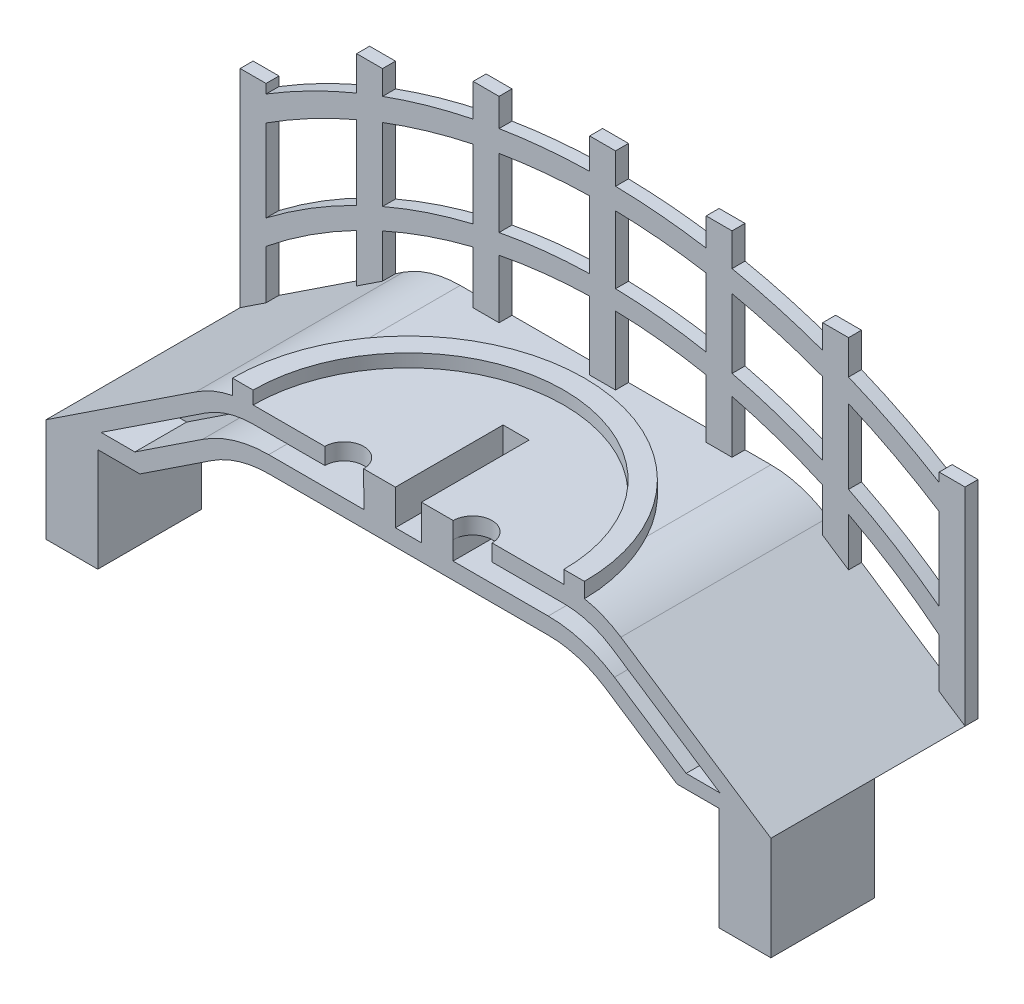
SolidWorks part; units mm, degrees
ref_plane "Front Plane" through (0, 0, 0) normal (0, 0, 1) x (1, 0, 0)
ref_plane "Top Plane" through (0, 0, 0) normal (0, 1, 0) x (1, 0, 0)
ref_plane "Right Plane" through (0, 0, 0) normal (1, 0, 0) x (0, 0, -1)
sketch "Sketch5" plane through (0, 0, 0) normal (0, 0, 1) x (1, 0, 0)
  line L0 (1.751, -2.6485) -> (10.1527, 2.906)
  line L1 (12.7, 7.134) -> (31.75, 7.134)
  line L2 (0, 0) -> (9.198, 6.081)
  line L3 (35.252, 6.081) -> (44.45, 0)
  line L4 (0, 0) -> (10.7907, 0) construction
  line L5 (44.45, 0) -> (33.6593, 0) construction
  line L6 (13.6546, 3.959) -> (30.7954, 3.959)
  line L7 (34.2973, 2.906) -> (42.699, -2.6485)
  line L8 (0, 0) -> (5.7571, 0)
  line L9 (44.45, 0) -> (38.6929, 0)
  line L10 (0, 0) -> (0, 9.525)
  line L11 (44.45, 0) -> (44.45, 9.525)
  line L12 (22.225, 7.134) -> (22.225, 16.659) construction
  line L13 (22.225, 7.134) -> (22.225, 3.959) construction
  line L14 (0, 0) -> (1.5875, 0)
  line L15 (0, 0) -> (0, 12.7)
  line L16 (0, 12.7) -> (1.5875, 12.7)
  line L17 (1.5875, 0) -> (1.5875, 12.7)
  line L18 (23.0187, 3.959) -> (21.4312, 3.959)
  line L19 (23.0187, 3.959) -> (23.0188, 19.834)
  line L20 (23.0188, 19.834) -> (21.4312, 19.834)
  line L21 (21.4312, 3.959) -> (21.4312, 19.834)
  line L22 (1.5875, 9.2118) -> (7.1438, 9.2118) construction
  line L23 (7.1437, 17.0604) -> (8.7312, 17.0604)
  line L24 (7.1437, 17.0604) -> (7.1438, 1.1854)
  line L25 (7.1438, 1.1854) -> (8.7313, 1.1854)
  line L26 (8.7312, 17.0604) -> (8.7313, 1.1854)
  line L27 (14.2875, 19.1598) -> (15.875, 19.1598)
  line L28 (14.2875, 19.1598) -> (14.2875, 3.2848)
  line L29 (14.2875, 3.2848) -> (15.875, 3.2848)
  line L30 (15.875, 19.1598) -> (15.875, 3.2848)
  line L31 (8.7313, 8.208) -> (14.2875, 8.208) construction
  line L32 (15.875, 13.1596) -> (21.4312, 13.1596) construction
  line L33 (7.9375, 17.0604) -> (7.9375, 13.8854) construction
  line L34 (15.0812, 19.1598) -> (15.0812, 15.9848) construction
  line L35 (44.45, 0) -> (38.6929, 0)
  line L36 (30.1625, 19.1598) -> (28.575, 19.1598)
  line L37 (30.1625, 19.1598) -> (30.1625, 3.2848)
  line L38 (28.575, 19.1598) -> (28.575, 3.2848)
  line L39 (30.1625, 3.2848) -> (28.575, 3.2848)
  line L40 (37.3062, 1.1854) -> (35.7187, 1.1854)
  line L41 (37.3062, 17.0604) -> (35.7187, 17.0604)
  line L42 (35.7187, 17.0604) -> (35.7187, 1.1854)
  line L43 (37.3062, 17.0604) -> (37.3062, 1.1854)
  line L44 (44.45, 12.7) -> (42.8625, 12.7)
  line L45 (44.45, 0) -> (44.45, 12.7)
  line L46 (44.45, 0) -> (44.45, 9.525)
  line L47 (42.8625, 0) -> (42.8625, 12.7)
  line L48 (11.7454, 3.959) -> (32.7046, 3.959) construction
  line L49 (32.7046, 3.959) -> (42.699, -2.6485) construction
  line L50 (10.7907, 7.134) -> (33.6593, 7.134) construction
  line L51 (33.6593, 7.134) -> (44.45, 0) construction
  line L52 (1.751, -2.6485) -> (11.7454, 3.959) construction
  line L53 (0, 0) -> (10.7907, 7.134) construction
  arc A0 (0, 9.525) -> (44.45, 9.525) centre (22.225, -21.5277) cw
  arc A1 (0, 11.1125) -> (44.45, 11.1125) centre (22.225, -21.5277) cw
  arc A2 (30.7954, 3.959) -> (34.2973, 2.906) centre (30.7954, -2.391) cw
  arc A3 (31.75, 7.134) -> (35.252, 6.081) centre (31.75, 0.784) cw
  arc A4 (10.1527, 2.906) -> (13.6546, 3.959) centre (13.6546, -2.391) cw
  arc A5 (12.7, 7.134) -> (9.198, 6.081) centre (12.7, 0.784) ccw
  point P65 (33.6593, 7.134)
  dimension "D12" = 6.35
  dimension "D2" = 19.05
  dimension "D1" = 44.45
  dimension "D3" = 3.175
  dimension "D4" = 9.525
  dimension "D5" = 1.5875
  dimension "D6" = 12.7
  dimension "D7" = 1.5875
  dimension "D8" = 15.875
  dimension "D9" = 12.7
  dimension "D10" = 3.175
  dimension "D11" = 1.5875
extrude "Boss-Extrude1" add sketch "Sketch5" along normal blind 12.7 contours L8 L17 L2 | L25 L24 L2 L17 L8 L0 | L26 L2 L24 L25 L0 | L1 A5 L2 L26 L0 A4 L6 L28 | L30 L1 L28 L6 | L1 L30 L6 L21 | L21 L6 L19 L1 | L38 L1 L19 L6 | L1 L38 L6 L37 | A3 L1 L37 L6 A2 L7 L42 L3 | L43 L3 L42 L7 L40 | L35 L47 L3 L43 L40 L7 | L47 L9 L3 region at (4.8921, 1.6908, 0) region at (7.9435, 3.3651, 0) region at (1.0583, 0.3498, 0) region at (11.4022, 5.0552, 0) region at (15.0812, 5.5465, 0) region at (18.6531, 5.5465, 0) region at (22.225, 5.5465, 0) region at (25.7969, 5.5465, 0) region at (29.3687, 5.5465, 0) region at (33.0478, 5.0552, 0) region at (36.5065, 3.3651, 0) region at (39.5579, 1.6908, 0) region at (43.3917, 0.3498, 0)
extrude "Boss-Extrude2" add sketch "Sketch5<4>" along normal blind 0.7937 separate body contours A1 L15 A0 L17 | A1 L17 A0 L24 | A1 L24 A0 L26 | A1 L26 A0 L28 | A1 L28 A0 L30 | A1 L30 A0 L21 | A1 L21 A0 L19 | A1 L19 A0 L38 | A1 L38 A0 L37 | A1 L37 A0 L42 | A1 L42 A0 L43 | A1 L43 A0 L47 | A1 L47 A0 L45 region at (0.7895, 10.851, 0) region at (4.3267, 12.8905, 0) region at (7.9352, 14.5811, 0) region at (11.4895, 15.7587, 0) region at (15.0802, 16.6439, 0) region at (18.647, 17.111, 0) region at (22.225, 17.3071, 0) region at (25.803, 17.111, 0) region at (29.3698, 16.6439, 0) region at (32.9605, 15.7587, 0) region at (36.5148, 14.5811, 0) region at (40.1233, 12.8905, 0) region at (43.6605, 10.851, 0)
sketch "Sketch5<4>" plane through (0, 0, 0) normal (0, 0, 1) x (1, 0, 0) same geometry as "Sketch5"
extrude "Boss-Extrude6" add sketch "Sketch5<7>" along normal blind 0.7937 contours L15 A1 L17 L16 | A0 L10 L2 L17 | A1 L15 A0 L17 | A0 L24 L2 L26 | L24 A1 L26 L23 | L26 L2 L24 L0 | L26 L0 L24 L25 | A1 L24 A0 L26 | L28 A1 L30 L27 | A1 L28 A0 L30 | A0 L28 L1 L30 | L30 L1 L28 L6 | L30 L6 L28 L29 | L21 L18 L19 L6 | L21 L6 L19 L1 | A0 L21 L1 L19 | L21 A1 L19 L20 | A1 L21 A0 L19 | L38 A1 L37 L36 | A0 L38 L1 L37 | L1 L38 L6 L37 | L39 L37 L6 L38 | L43 L7 L42 L40 | L43 L3 L42 L7 | A0 L42 L3 L43 | A1 L42 A0 L43 | L42 A1 L43 L41 | L47 A1 L45 L44 | A1 L47 A0 L45 | A0 L47 L3 L11 | L47 L9 L3 region at (7.9435, 3.3651, 0) region at (8.3375, 1.4457, 0) region at (0.7941, 5.2992, 0) region at (7.9312, 9.5615, 0) region at (0.7895, 10.851, 0) region at (7.9352, 14.5811, 0) region at (0.6663, 12.1261, 0) region at (15.0812, 5.5465, 0) region at (15.0812, 3.6219, 0) region at (7.8917, 16.1623, 0) region at (15.0858, 11.5584, 0) region at (15.0802, 16.6439, 0) region at (15.0604, 18.2312, 0) region at (22.225, 5.5465, 0) region at (22.225, 11.8951, 0) region at (22.225, 17.3071, 0) region at (22.225, 18.896, 0) region at (29.3687, 5.5465, 0) region at (29.3687, 3.6219, 0) region at (29.3642, 11.5584, 0) region at (29.3896, 18.2312, 0) region at (36.5188, 9.5615, 0) region at (36.5148, 14.5811, 0) region at (36.5583, 16.1623, 0) region at (36.5065, 3.3651, 0) region at (36.1125, 1.4457, 0) region at (43.6559, 5.2992, 0) region at (43.6605, 10.851, 0) region at (43.7837, 12.1261, 0) region at (43.3917, 0.3498, 0)
sketch "Sketch5<7>" plane through (0, 0, 0) normal (0, 0, 1) x (1, 0, 0) same geometry as "Sketch5"
sketch "Sketch6" plane through (0, 0, 0) normal (0, 0, -1) x (-1, 0, 0)
  line L0 (-44.45, 0) -> (-44.45, 12.7) construction
  line L1 (0, 0) -> (0, 12.7) construction
  line L2 (-44.45, 4.2704) -> (-44.45, 2.6829)
  line L3 (0, 2.6829) -> (0, 4.2704)
  arc A0 (-44.45, 4.2704) -> (0, 4.2704) centre (-22.225, -21.5277) cw
  arc A1 (-44.45, 2.6829) -> (0, 2.6829) centre (-22.225, -21.5277) cw
  arc A2 (-23.0187, 16.6507) -> (-28.575, 16.1273) centre (-22.225, -21.5277) ccw construction
  dimension "D1" = 1.5875
extrude "Boss-Extrude7" add sketch "Sketch6" against normal blind 0.7937
sketch "Sketch7" plane through (0, 0, 12.7) normal (0, 0, 1) x (1, 0, 0)
  line L0 (22.225, 7.134) -> (12.7, 7.134)
  line L1 (12.7, 7.134) -> (31.75, 7.134) construction
  line L2 (12.7, 7.134) -> (12.7, 6.118)
  line L3 (13.6546, 3.959) -> (30.7954, 3.959) construction
  line L5 (12.7, 6.118) -> (12.7, 4.975)
  line L6 (12.7, 4.975) -> (31.75, 4.975)
  line L7 (31.75, 6.118) -> (31.75, 4.975)
  line L9 (35.252, 6.081) -> (44.45, 0) construction
  line L10 (44.45, 0) -> (38.6929, 0) construction
  line L13 (31.75, 4.975) -> (30.7954, 4.975)
  line L14 (31.75, 6.118) -> (12.7, 6.118)
  line L16 (39.2532, 0.8475) -> (41.3258, 0.8475)
  line L17 (34.8577, 3.7535) -> (39.2532, 0.8475)
  line L18 (34.8577, 3.7535) -> (39.2532, 0.8475)
  line L20 (3.3791, 1.016) -> (5.4516, 1.016)
  line L21 (5.4516, 1.016) -> (9.5923, 3.7535)
  line L22 (9.7583, 5.2335) -> (3.3791, 1.016)
  line L23 (3.3791, 1.016) -> (5.4516, 1.016)
  line L24 (5.4516, 1.016) -> (9.5923, 3.7535)
  line L25 (9.7583, 5.2335) -> (3.3791, 1.016)
  line L41 (40.5352, 0) -> (42.6077, 0)
  line L42 (42.6077, 0) -> (34.6917, 5.2335)
  arc A8 (13.6546, 4.975) -> (9.5923, 3.7535) centre (13.6546, -2.391) ccw
  arc A9 (12.7, 6.118) -> (9.7583, 5.2335) centre (12.7, 0.784) ccw
  arc A10 (13.6546, 4.975) -> (9.5923, 3.7535) centre (13.6546, -2.391) ccw
  arc A11 (12.7, 6.118) -> (9.7583, 5.2335) centre (12.7, 0.784) ccw
  arc A12 (34.8577, 3.7535) -> (30.7954, 4.975) centre (30.7954, -2.391) ccw
  arc A13 (34.8577, 3.7535) -> (30.7954, 4.975) centre (30.7954, -2.391) ccw
  arc A16 (34.6917, 5.2335) -> (31.75, 6.118) centre (31.75, 0.784) ccw
  arc A17 (34.6917, 5.2335) -> (31.75, 6.118) centre (31.75, 0.784) ccw
  dimension "D6" = 1.016
  dimension "D1" = 9.525
  dimension "D2" = 1.016
  dimension "D3" = 1.016
  dimension "D4" = 19.05
  dimension "D7" = 1.016
  dimension "D5" = 1.016
  dimension "D8" = 1.016
  dimension "D9" = 1.016
extrude "Cut-Extrude1" cut sketch "Sketch7" against normal blind 9.525 contours L7 L5 L6 region at (22.225, 5.5465, 12.7)
sketch "Sketch8" plane through (0, 7.134, 0) normal (0, 1, 0) x (1, 0, 0)
  line L0 (12.7, -12.7) -> (31.75, -12.7) construction
  line L1 (18.288, -12.7) -> (12.7, -12.7)
  line L2 (26.162, -12.7) -> (31.75, -12.7)
  line L4 (23.0251, -19.304) -> (21.4249, -19.304)
  line L5 (23.0251, -19.304) -> (23.0251, -6.096)
  line L6 (23.0251, -6.096) -> (21.4249, -6.096)
  line L7 (21.4249, -19.304) -> (21.4249, -6.096)
  line L8 (23.0251, -19.304) -> (21.4249, -6.096) construction
  line L9 (23.0251, -6.096) -> (21.4249, -19.304) construction
  circle A0 centre (18.288, -12.7) radius 1.1906
  circle A1 centre (26.162, -12.7) radius 1.1906
  point P8 (22.225, -12.7)
  line M5 (12.7, -12.7) -> (31.75, -12.7)
  dimension "D1" = 2.3813
  dimension "D2" = 2.3813
  dimension "D3" = 5.588
  dimension "D4" = 1.6002
  dimension "D5" = 13.208
extrude "Cut-Extrude2" cut sketch "Sketch8" against normal blind 1.397 contours A0 L1 M5 | A1 M5 | L7 L5 L6 M5 region at (18.288, 7.134, 12.1947) region at (26.162, 7.134, 12.1947) region at (22.225, 7.134, 9.398)
sketch "Sketch10" plane through (0, 4.975, 0) normal (0, 1, 0) x (1, 0, 0)
  line L0 (12.7, -12.7) -> (31.75, -12.7) construction
  line L1 (19.4888, -19.9033) -> (24.9612, -19.9033)
  line L2 (19.4888, -19.9033) -> (19.4888, -5.4967)
  line L3 (19.4888, -5.4967) -> (24.9612, -5.4967)
  line L4 (24.9612, -19.9033) -> (24.9612, -5.4967)
  line L5 (19.4888, -19.9033) -> (24.9612, -5.4967) construction
  line L6 (19.4888, -5.4967) -> (24.9612, -19.9033) construction
  line L7 (24.9612, -12.7) -> (19.4888, -12.7)
  line L8 (23.0251, -19.304) -> (21.4249, -19.304)
  line L9 (23.0251, -19.304) -> (23.0251, -6.096)
  line L10 (23.0251, -6.096) -> (21.4249, -6.096)
  line L11 (21.4249, -19.304) -> (21.4249, -6.096)
  line L12 (23.0251, -19.304) -> (21.4249, -6.096) construction
  line L13 (23.0251, -6.096) -> (21.4249, -19.304) construction
  line L14 (19.4786, -12.7) -> (21.4249, -12.7) construction
  point P0 (22.225, -12.7)
  point P7 (22.225, -12.7)
  line M1 (12.7, -12.7) -> (31.75, -12.7)
extrude "Boss-Extrude8" add sketch "Sketch10" along normal blind 1.397 contours L11 L10 L9 L7 L4 L3 L2 M1 region at (19.5792, 4.975, 9.0984)
sketch "Sketch11" plane through (0, 7.134, 0) normal (0, 1, 0) x (1, 0, 0)
  line L0 (21.4249, -12.7) -> (23.0251, -12.7) construction
  line L1 (11.43, -12.7) -> (33.02, -12.7)
  circle A0 centre (22.225, -12.7) radius 9.525
  circle A1 centre (22.225, -12.7) radius 10.795
  line M9 (31.75, -12.7) -> (31.75, 0)
  line M19 (12.7, 0) -> (12.7, -12.7)
  dimension "D1" = 19.05
  dimension "D2" = 21.59
extrude "Boss-Extrude9" add sketch "Sketch11" along normal blind 0.7937 and the other way blind 0.254 contours A1 A0 M9 M19 | A1 L1 M19 | L1 A1 M9 region at (12.1893, 7.134, 10.7791) region at (12.919, 7.134, 10.16) region at (32.2607, 7.134, 10.7791)
sketch "Sketch12" plane through (0, 0, 0) normal (0, -1, 0) x (1, 0, 0)
  line L1 (0, 12.7) -> (3.175, 12.7)
  line L2 (0, 12.7) -> (0, 6.35)
  line L3 (0, 6.35) -> (3.175, 6.35)
  line L4 (3.175, 12.7) -> (3.175, 6.35)
  line L5 (44.45, 12.7) -> (41.275, 12.7)
  line L6 (44.45, 12.7) -> (44.45, 6.35)
  line L7 (44.45, 6.35) -> (41.275, 6.35)
  line L8 (41.275, 12.7) -> (41.275, 6.35)
  dimension "D1" = 3.175
  dimension "D2" = 6.35
  dimension "D3" = 6.35
  dimension "D4" = 3.175
extrude "Boss-Extrude10" add sketch "Sketch12" along normal blind 6.35
sketch "Sketch14" plane through (0, 0, 12.7) normal (0, 0, 1) x (1, 0, 0)
extrude "Cut-Extrude3" cut sketch "Sketch7<4>" against normal blind 3.175 contours L5 A11 L25 L23 L24 A10 L6 | L42 L7 L6 L41 region at (8.5031, 3.6264, 12.7) region at (36.0738, 3.5452, 12.7)
sketch "Sketch7<4>" plane through (0, 0, 12.7) normal (0, 0, 1) x (1, 0, 0) same geometry as "Sketch7"
sketch "Sketch16" plane through (0, 7.134, 0) normal (0, 1, 0) x (1, 0, 0)
  line L0 (13.6546, -12.7) -> (19.4888, -12.7) construction
  line L1 (21.4249, -6.096) -> (16.6624, -6.096)
  line L2 (21.4249, -6.096) -> (21.4249, -12.7)
  line L3 (21.4249, -12.7) -> (16.6624, -12.7)
  line L4 (16.6624, -6.096) -> (16.6624, -12.7)
  dimension "D1" = 4.7625
